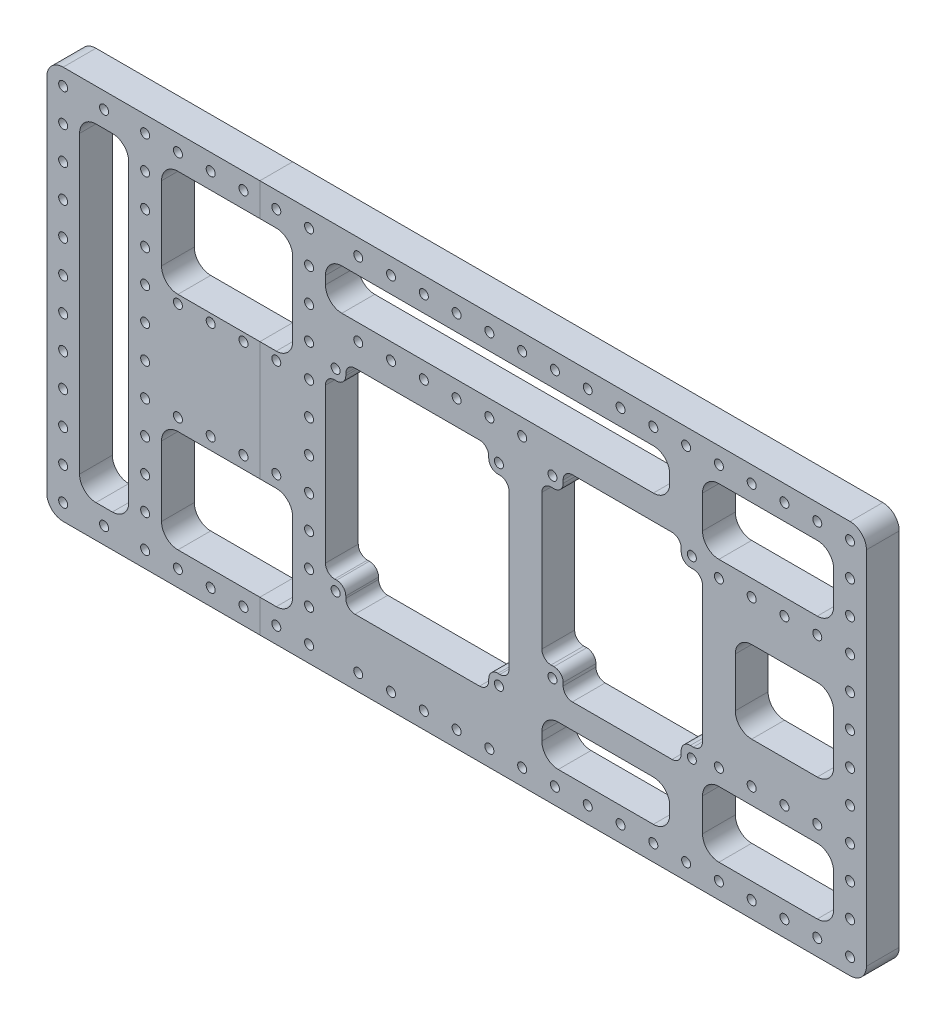
SolidWorks part; units mm, degrees
ref_plane "Alzado" through (0, 0, 0) normal (0, 0, 1) x (1, 0, 0)
ref_plane "Planta" through (0, 0, 0) normal (0, 1, 0) x (1, 0, 0)
ref_plane "Vista lateral" through (0, 0, 0) normal (1, 0, 0) x (0, 0, -1)
sketch "Croquis1" plane through (0, 0, 0) normal (0, 0, 1) x (1, 0, 0)
  line L1 (0, 0) -> (250, 0)
  line L2 (0, 0) -> (0, 120)
  line L3 (0, 120) -> (250, 120)
  line L4 (250, 0) -> (250, 120)
  dimension "D1" = 250
  dimension "D2" = 120
extrude "Saliente-Extruir1" add sketch "Croquis1" along normal blind 10
sketch "Croquis2" plane through (0, 0, 10) normal (0, 0, 1) x (1, 0, 0)
  line L0 (10, 110) -> (10, 10)
  line L1 (35, 110) -> (75, 110)
  line L2 (10, 10) -> (25, 10)
  line L3 (25, 110) -> (25, 10)
  line L5 (10, 110) -> (25, 110)
  line L6 (85, 110) -> (85, 97.5)
  line L7 (35, 10) -> (75, 10)
  line L8 (35, 10) -> (35, 110)
  line L9 (75, 110) -> (75, 10)
  line L10 (141, 20) -> (141, 85)
  line L11 (85, 110) -> (141, 110)
  line L12 (141, 20) -> (85, 20)
  line L13 (141, 85) -> (85, 85)
  line L14 (85, 85) -> (85, 20)
  line L15 (85, 97.5) -> (141, 97.5)
  line L16 (141, 97.5) -> (141, 110)
  line L18 (151, 25) -> (151, 95)
  line L23 (151, 95) -> (201, 95)
  line L24 (201, 95) -> (201, 25)
  line L25 (201, 25) -> (151, 25)
  dimension "D1" = 100
  dimension "D2" = 15
  dimension "D4" = 10
  dimension "D5" = 40
  dimension "D6" = 65
  dimension "D7" = 56
extrude "Cortar-Extruir1" cut sketch "Croquis2" against normal through all
sketch "Croquis6" plane through (0, 0, 10) normal (0, 0, 1) x (1, 0, 0)
  line L0 (75, 97.5) -> (35, 97.5)
  line L1 (75, 10) -> (75, 110) construction
  line L2 (35, 110) -> (35, 10) construction
  line L3 (35, 97.5) -> (35, 85)
  line L4 (35, 85) -> (75, 85)
  line L5 (75, 85) -> (75, 97.5)
extrude "Saliente-Extruir3" add sketch "Croquis6" against normal blind 10
sketch "Croquis7" plane through (0, 0, 10) normal (0, 0, 1) x (1, 0, 0)
  line L0 (151, 25) -> (151, 30)
  line L1 (151, 95) -> (151, 25) construction
  line L2 (151, 30) -> (201, 30)
  line L3 (201, 25) -> (201, 95) construction
  line L4 (201, 30) -> (201, 25)
  line L5 (201, 25) -> (151, 25)
  dimension "D1" = 5
extrude "Saliente-Extruir4" add sketch "Croquis7" against normal blind 10
sketch "Croquis8" plane through (0, 0, 10) normal (0, 0, 1) x (1, 0, 0)
  line L0 (151, 95) -> (151, 90)
  line L1 (151, 95) -> (151, 30) construction
  line L2 (151, 90) -> (201, 90)
  line L3 (201, 30) -> (201, 95) construction
  line L4 (201, 90) -> (201, 95)
  line L5 (201, 95) -> (151, 95)
  dimension "D1" = 5
extrude "Saliente-Extruir5" add sketch "Croquis8" against normal blind 10
sketch "Croquis10" plane through (0, 0, 10) normal (0, 0, 1) x (1, 0, 0)
  line L0 (200, 90) -> (200, 30)
  line L2 (240, 110) -> (200, 110)
  line L3 (201, 30) -> (151, 30) construction
  line L4 (200, 110) -> (200, 97.5)
  line L5 (200, 97.5) -> (240, 97.5)
  line L6 (240, 97.5) -> (240, 110)
  line L7 (200, 30) -> (201, 30)
  line L8 (151, 90) -> (201, 90) construction
  line L9 (200, 90) -> (201, 90)
  line L10 (201, 90) -> (201, 30)
  dimension "D1" = 1
  dimension "D2" = 40
extrude "Saliente-Extruir6" add sketch "Croquis10" against normal blind 10
sketch "Croquis11" plane through (0, 0, 10) normal (0, 0, 1) x (1, 0, 0)
  line L1 (200, 97.5) -> (200, 110)
  line L2 (200, 110) -> (240, 110)
  line L3 (240, 110) -> (240, 97.5)
  line L4 (240, 97.5) -> (200, 97.5)
  line L7 (240, 10) -> (240, 22.5)
  line L8 (240, 22.5) -> (200, 22.5)
  line L9 (200, 22.5) -> (200, 10)
  line L10 (200, 10) -> (240, 10)
  dimension "D1" = 40
extrude "Cortar-Extruir3" cut sketch "Croquis11" against normal through all
sketch "Croquis12" plane through (0, 0, 10) normal (0, 0, 1) x (1, 0, 0)
  line L1 (35, 85) -> (35, 10) construction
  line L2 (35, 72.5) -> (75, 72.5)
  line L3 (75, 10) -> (75, 85) construction
  line L4 (75, 72.5) -> (75, 85)
  line L5 (75, 85) -> (35, 85)
  line L6 (35, 85) -> (35, 72.5)
extrude "Saliente-Extruir7" add sketch "Croquis12" against normal blind 10
sketch "Croquis13" plane through (0, 0, 10) normal (0, 0, 1) x (1, 0, 0)
  line L1 (35, 72.5) -> (35, 10) construction
  line L2 (35, 47.5) -> (75, 47.5)
  line L3 (75, 10) -> (75, 72.5) construction
  line L4 (75, 47.5) -> (75, 22.5)
  line L5 (75, 22.5) -> (35, 22.5)
  line L6 (35, 22.5) -> (35, 47.5)
  dimension "D2" = 25
extrude "Saliente-Extruir9" add sketch "Croquis13" against normal blind 10
sketch "Croquis14" plane through (0, 0, 10) normal (0, 0, 1) x (1, 0, 0)
  line L0 (151, 110) -> (141, 110)
  line L1 (141, 110) -> (141, 97.5)
  line L2 (210, 30) -> (240, 30)
  line L3 (210, 30) -> (210, 90)
  line L4 (210, 90) -> (240, 90)
  line L5 (240, 30) -> (240, 90)
  line L6 (141, 97.5) -> (141, 110) construction
  line L7 (151, 110) -> (190, 110)
  line L8 (141, 97.5) -> (151, 97.5)
  line L9 (151, 97.5) -> (190, 97.5)
  line L10 (190, 110) -> (190, 97.5)
  line L11 (190, 22.5) -> (151, 22.5)
  line L12 (151, 22.5) -> (151, 10)
  line L13 (151, 10) -> (190, 10)
  line L14 (190, 10) -> (190, 22.5)
  dimension "D1" = 60
extrude "Cortar-Extruir4" cut sketch "Croquis14" against normal through all
fillet "Redondeo4" radius 5 38 edges at (10, 110, 5) (35, 72.5, 5) (85, 97.5, 5) (35, 110, 5) (85, 110, 5) (200, 22.5, 5) (210, 90, 5) (200, 110, 5) (210, 30, 5) (240, 30, 5) (240, 10, 5) (240, 97.5, 5) (190, 10, 5) (190, 97.5, 5) (25, 10, 5) (75, 97.5, 5) (75, 47.5, 5) (75, 10, 5) (10, 10, 5) (35, 97.5, 5) (35, 47.5, 5) (35, 10, 5) (151, 10, 5) (200, 10, 5) (200, 97.5, 5) (190, 22.5, 5) (240, 22.5, 5) (240, 90, 5) (240, 110, 5) (190, 110, 5) (75, 22.5, 5) (75, 72.5, 5) (75, 110, 5) (25, 110, 5) (0, 120, 5) (0, 0, 5) (250, 0, 5) (250, 120, 5)
fillet "Redondeo5" radius 5 2 edges at (35, 22.5, 5) (151, 22.5, 5)
sketch "Croquis16" plane through (0, 0, 10) normal (0, 0, 1) x (1, 0, 0)
  line L0 (85, 20) -> (91.2, 20)
  line L1 (85, 20) -> (141, 20) construction
  line L2 (91.2, 20) -> (91.2, 26.2)
  line L3 (91.2, 26.2) -> (85, 26.2)
  line L4 (85, 85) -> (85, 20) construction
  line L5 (85, 26.2) -> (85, 20)
  line L9 (134.8, 26.2) -> (141, 26.2)
  line L10 (141, 20) -> (134.8, 20)
  line L11 (141, 26.2) -> (141, 20)
  line L12 (134.8, 20) -> (134.8, 26.2)
  line L13 (141, 78.8) -> (141, 85)
  line L14 (134.8, 78.8) -> (141, 78.8)
  line L15 (134.8, 85) -> (134.8, 78.8)
  line L16 (141, 85) -> (134.8, 85)
  line L17 (85, 85) -> (91.2, 85)
  line L18 (85, 78.8) -> (85, 85)
  line L19 (91.2, 78.8) -> (85, 78.8)
  line L20 (91.2, 85) -> (91.2, 78.8)
  dimension "D1" = 6.2
  dimension "D2" = 6.2
extrude "Saliente-Extruir10" add sketch "Croquis16" against normal blind 10
sketch "Croquis17" plane through (0, 0, 10) normal (0, 0, 1) x (1, 0, 0)
  line L1 (151, 90) -> (157.5, 90)
  line L2 (151, 90) -> (151, 83.5)
  line L3 (151, 83.5) -> (157.5, 83.5)
  line L4 (157.5, 90) -> (157.5, 83.5)
  line L10 (151, 30) -> (151, 36.5)
  line L11 (151, 30) -> (157.5, 30)
  line L12 (157.5, 30) -> (157.5, 36.5)
  line L13 (151, 36.5) -> (157.5, 36.5)
  line L14 (193.5, 90) -> (193.5, 83.5)
  line L15 (200, 83.5) -> (193.5, 83.5)
  line L16 (200, 90) -> (200, 83.5)
  line L17 (200, 90) -> (193.5, 90)
  line L18 (200, 36.5) -> (193.5, 36.5)
  line L19 (193.5, 30) -> (193.5, 36.5)
  line L20 (200, 30) -> (193.5, 30)
  line L21 (200, 30) -> (200, 36.5)
  dimension "D1" = 6.5
  dimension "D2" = 6.5
extrude "Saliente-Extruir12" add sketch "Croquis17" against normal blind 10
fillet "Redondeo6" radius 2.8 8 edges at (157.5, 83.5, 5) (157.5, 36.5, 5) (193.5, 36.5, 5) (193.5, 83.5, 5) (134.8, 26.2, 5) (134.8, 78.8, 5) (91.2, 26.2, 5) (91.2, 78.8, 5)
fillet "Redondeo7" radius 2.8 14 edges at (193.5, 30, 5) (200, 36.5, 5) (200, 83.5, 5) (193.5, 90, 5) (134.8, 85, 5) (141, 78.8, 5) (141, 26.2, 5) (134.8, 20, 5) (157.5, 30, 5) (151, 36.5, 5) (91.2, 20, 5) (85, 26.2, 5) (85, 78.8, 5) (91.2, 85, 5)
fillet "Redondeo8" radius 2.8 2 edges at (151, 83.5, 5) (157.5, 90, 5)
sketch "Croquis18" plane through (0, 0, 10) normal (0, 0, 1) x (1, 0, 0)
  circle A0 centre (137.9, 23.1) radius 1.375
  circle A1 centre (88.1, 23.1) radius 1.375
  circle A2 centre (88.1, 81.9) radius 1.375
  circle A3 centre (137.9, 81.9) radius 1.375
  circle A4 centre (154.25, 33.25) radius 1.375
  circle A5 centre (196.75, 33.25) radius 1.375
  circle A6 centre (196.75, 86.75) radius 1.375
  circle A7 centre (154.25, 86.75) radius 1.375
  dimension "D1" = 2.75
extrude "Cortar-Extruir5" cut sketch "Croquis18" against normal through all
sketch "Croquis19" plane through (0, 0, 10) normal (0, 0, 1) x (1, 0, 0)
  line L0 (240, 72.5) -> (210, 72.5)
  line L1 (240, 35) -> (240, 85) construction
  line L3 (240, 47.5) -> (210, 47.5)
  line L4 (210, 30) -> (240, 30)
  line L5 (240, 90) -> (240, 72.5)
  line L6 (240, 30) -> (240, 47.5)
  line L7 (210, 85) -> (210, 35) construction
  line L8 (210, 72.5) -> (210, 90)
  line L9 (210, 90) -> (240, 90)
  line L10 (210, 47.5) -> (210, 30)
extrude "Saliente-Extruir13" add sketch "Croquis19" against normal blind 10
sketch "Croquis20" plane through (0, 0, 10) normal (0, 0, 1) x (1, 0, 0)
  line L0 (200, 10) -> (240, 10)
  line L2 (200, 10) -> (200, 30)
  line L3 (200, 30) -> (240, 30)
  line L4 (240, 10) -> (240, 30)
  line L7 (240, 110) -> (240, 90)
  line L8 (200, 90) -> (240, 90)
  line L9 (200, 110) -> (200, 90)
  line L10 (200, 110) -> (240, 110)
extrude "Cortar-Extruir7" cut sketch "Croquis20" against normal through all
fillet "Redondeo9" radius 5 12 edges at (200, 10, 5) (210, 47.5, 5) (200, 90, 5) (240, 10, 5) (240, 47.5, 5) (240, 90, 5) (240, 30, 5) (240, 72.5, 5) (240, 110, 5) (200, 30, 5) (200, 110, 5) (210, 72.5, 5)
sketch "Croquis21" plane through (0, 0, 10) normal (0, 0, 1) x (1, 0, 0)
  circle A2 centre (5, 115) radius 1.375
  circle A3 centre (5, 105) radius 1.375
  circle A4 centre (5, 95) radius 1.375
  circle A5 centre (5, 85) radius 1.375
  circle A6 centre (5, 75) radius 1.375
  circle A7 centre (5, 65) radius 1.375
  circle A8 centre (5, 55) radius 1.375
  circle A9 centre (5, 45) radius 1.375
  circle A10 centre (5, 35) radius 1.375
  circle A11 centre (5, 25) radius 1.375
  circle A12 centre (5, 15) radius 1.375
  circle A13 centre (5, 5) radius 1.375
  circle A14 centre (245, 5) radius 1.375
  circle A15 centre (245, 15) radius 1.375
  circle A16 centre (245, 25) radius 1.375
  circle A17 centre (245, 35) radius 1.375
  circle A18 centre (245, 45) radius 1.375
  circle A19 centre (245, 55) radius 1.375
  circle A20 centre (245, 65) radius 1.375
  circle A21 centre (245, 75) radius 1.375
  circle A22 centre (245, 85) radius 1.375
  circle A23 centre (245, 95) radius 1.375
  circle A24 centre (245, 105) radius 1.375
  circle A25 centre (245, 115) radius 1.375
  circle A26 centre (15, 115) radius 1.375
  circle A27 centre (25, 115) radius 1.375
  circle A28 centre (35, 115) radius 1.375
  circle A29 centre (45, 115) radius 1.375
  circle A30 centre (55, 115) radius 1.375
  circle A31 centre (65, 115) radius 1.375
  circle A32 centre (75, 115) radius 1.375
  circle A33 centre (85, 115) radius 1.375
  circle A34 centre (95, 115) radius 1.375
  circle A35 centre (105, 115) radius 1.375
  circle A36 centre (115, 115) radius 1.375
  circle A37 centre (125, 115) radius 1.375
  circle A38 centre (135, 115) radius 1.375
  circle A39 centre (145, 115) radius 1.375
  circle A40 centre (155, 115) radius 1.375
  circle A41 centre (165, 115) radius 1.375
  circle A42 centre (175, 115) radius 1.375
  circle A43 centre (185, 115) radius 1.375
  circle A44 centre (195, 115) radius 1.375
  circle A45 centre (205, 115) radius 1.375
  circle A46 centre (215, 115) radius 1.375
  circle A47 centre (225, 115) radius 1.375
  circle A48 centre (235, 115) radius 1.375
  circle A49 centre (235, 5) radius 1.375
  circle A50 centre (225, 5) radius 1.375
  circle A51 centre (215, 5) radius 1.375
  circle A52 centre (205, 5) radius 1.375
  circle A53 centre (195, 5) radius 1.375
  circle A54 centre (185, 5) radius 1.375
  circle A55 centre (175, 5) radius 1.375
  circle A56 centre (165, 5) radius 1.375
  circle A57 centre (155, 5) radius 1.375
  circle A58 centre (145, 5) radius 1.375
  circle A59 centre (135, 5) radius 1.375
  circle A60 centre (125, 5) radius 1.375
  circle A61 centre (115, 5) radius 1.375
  circle A62 centre (105, 5) radius 1.375
  circle A63 centre (95, 5) radius 1.375
  circle A64 centre (85, 5) radius 1.375
  circle A65 centre (75, 5) radius 1.375
  circle A66 centre (65, 5) radius 1.375
  circle A67 centre (55, 5) radius 1.375
  circle A68 centre (45, 5) radius 1.375
  circle A69 centre (35, 5) radius 1.375
  circle A70 centre (25, 5) radius 1.375
  circle A71 centre (15, 5) radius 1.375
  dimension "D1" = 24
  dimension "D2" = 12
extrude "Cortar-Extruir8" cut sketch "Croquis21" against normal through all
sketch "Croquis22" plane through (0, 0, 10) normal (0, 0, 1) x (1, 0, 0)
  line L0 (35, 16.25) -> (75, 16.25)
  line L1 (35, 17.5) -> (35, 15) construction
  line L2 (75, 15) -> (75, 17.5) construction
  line L3 (75, 16.25) -> (75, 38.2484)
  line L4 (35, 102.5) -> (35, 16.25)
  line L5 (35, 102.5) -> (75, 102.5)
  line L6 (75, 102.5) -> (75, 38.2484)
extrude "Saliente-Extruir14" add sketch "Croquis22" against normal blind 10
sketch "Croquis23" plane through (0, 0, 10) normal (0, 0, 1) x (1, 0, 0)
  line L1 (35, 16.25) -> (75, 16.25)
  line L2 (35, 16.25) -> (35, 41.25)
  line L3 (35, 41.25) -> (75, 41.25)
  line L4 (75, 16.25) -> (75, 41.25)
  line L5 (35, 102.5) -> (75, 102.5)
  line L6 (35, 102.5) -> (35, 77.5)
  line L7 (35, 77.5) -> (75, 77.5)
  line L8 (75, 102.5) -> (75, 77.5)
  dimension "D1" = 25
  dimension "D2" = 25
extrude "Cortar-Extruir9" cut sketch "Croquis23" against normal through all
fillet "Redondeo10" radius 5 4 edges at (35, 77.5, 5) (75, 77.5, 5) (75, 41.25, 5) (35, 41.25, 5)
sketch "Croquis24" plane through (0, 0, 10) normal (0, 0, 1) x (1, 0, 0)
  circle A0 centre (30, 105) radius 1.375
  circle A1 centre (30, 95) radius 1.375
  circle A2 centre (30, 85) radius 1.375
  circle A3 centre (30, 75) radius 1.375
  circle A4 centre (30, 65) radius 1.375
  circle A5 centre (30, 55) radius 1.375
  circle A6 centre (30, 45) radius 1.375
  circle A7 centre (30, 35) radius 1.375
  circle A8 centre (30, 25) radius 1.375
  circle A9 centre (30, 15) radius 1.375
  dimension "D1" = 2.75
  dimension "D2" = 10
extrude "Cortar-Extruir10" cut sketch "Croquis24" against normal through all
sketch "Croquis25" plane through (0, 0, 10) normal (0, 0, 1) x (1, 0, 0)
  circle A0 centre (80, 75) radius 1.375
  circle A1 centre (80, 65) radius 1.375
  circle A2 centre (80, 55) radius 1.375
  circle A3 centre (80, 45) radius 1.375
  circle A4 centre (80, 85) radius 1.375
  circle A5 centre (80, 95) radius 1.375
  circle A6 centre (80, 105) radius 1.375
  circle A7 centre (80, 35) radius 1.375
  circle A8 centre (80, 25) radius 1.375
  circle A9 centre (80, 15) radius 1.375
  dimension "D1" = 2.75
  dimension "D2" = 4
  dimension "D3" = 3
  dimension "D4" = 2
  dimension "D5" = 4
extrude "Cortar-Extruir12" cut sketch "Croquis25" against normal through all
sketch "Croquis26" plane through (0, 0, 10) normal (0, 0, 1) x (1, 0, 0)
  circle A1 centre (183.625, 93.6429) radius 1.375
  circle A2 centre (173.625, 93.6429) radius 1.375
  circle A3 centre (163.625, 93.6429) radius 1.375
  circle A4 centre (153.625, 93.6429) radius 1.375
  circle A5 centre (143.625, 93.6429) radius 1.375
  circle A6 centre (133.625, 93.6429) radius 1.375
  circle A7 centre (123.625, 93.6429) radius 1.375
  circle A8 centre (113.625, 93.6429) radius 1.375
  circle A9 centre (103.625, 93.6429) radius 1.375
  circle A10 centre (93.625, 93.6429) radius 1.375
  dimension "D1" = 2.75
  dimension "D2" = 10
extrude "Cortar-Extruir13" cut sketch "Croquis26" against normal through all
sketch "Croquis29" plane through (0, 0, 10) normal (0, 0, 1) x (1, 0, 0)
  circle A0 centre (70, 75) radius 1.375
  circle A1 centre (40, 45) radius 1.375
  circle A2 centre (50, 45) radius 1.375
  circle A3 centre (60, 45) radius 1.375
  circle A4 centre (70, 45) radius 1.375
  circle A5 centre (60, 75) radius 1.375
  circle A6 centre (50, 75) radius 1.375
  circle A7 centre (40, 75) radius 1.375
extrude "Cortar-Extruir14" cut sketch "Croquis29" against normal blind 10
sketch "Croquis30" plane through (0, 0, 10) normal (0, 0, 1) x (1, 0, 0)
  circle A0 centre (205, 35) radius 1.375
  circle A1 centre (235, 85) radius 1.375
  circle A2 centre (225, 85) radius 1.375
  circle A3 centre (215, 85) radius 1.375
  circle A4 centre (205, 85) radius 1.375
  circle A5 centre (215, 35) radius 1.375
  circle A6 centre (225, 35) radius 1.375
  circle A7 centre (235, 35) radius 1.375
extrude "Cortar-Extruir15" cut sketch "Croquis30" against normal through all
sketch "Croquis35" plane through (0, 0, 10) normal (0, 0, 1) x (1, 0, 0)
  line L1 (11.3529, 7.7785) -> (198.8215, 7.7785)
  line L2 (11.3529, 7.7785) -> (11.3529, 2.2832)
  line L3 (11.3529, 2.2832) -> (198.8215, 2.2832)
  line L4 (198.8215, 7.7785) -> (198.8215, 2.2832)
  line L5 (11.3529, 118.1029) -> (87.653, 118.1029)
  line L6 (11.3529, 118.1029) -> (11.3529, 112.0945)
  line L7 (11.3529, 112.0945) -> (87.653, 112.0945)
  line L8 (87.653, 118.1029) -> (87.653, 112.0945)
extrude "Saliente-Extruir18" add sketch "Croquis35" against normal blind 10
sketch "Croquis36" plane through (0, 0, 10) normal (0, 0, 1) x (1, 0, 0)
  circle A0 centre (70, 115) radius 1.375
  circle A1 centre (60, 115) radius 1.375
  circle A2 centre (50, 115) radius 1.375
  circle A3 centre (40, 115) radius 1.375
  circle A4 centre (30, 115) radius 1.375
  circle A5 centre (80, 115) radius 1.375
  circle A6 centre (80, 5) radius 1.375
  circle A7 centre (30, 5) radius 1.375
  circle A8 centre (40, 5) radius 1.375
  circle A9 centre (50, 5) radius 1.375
  circle A10 centre (60, 5) radius 1.375
  circle A11 centre (70, 5) radius 1.375
  circle A12 centre (17.484, 5.0668) radius 1.375
  circle A13 centre (17.4813, 115.0286) radius 1.375
  dimension "D1" = 2.75
  dimension "D2" = 5
  dimension "D3" = 2
extrude "Cortar-Extruir16" cut sketch "Croquis36" against normal through all
sketch "Croquis37" plane through (0, 0, 10) normal (0, 0, 1) x (1, 0, 0)
  line L1 (87.3781, 96.1662) -> (187.5191, 96.1662)
  line L2 (87.3781, 96.1662) -> (87.3781, 91.7523)
  line L3 (87.3781, 91.7523) -> (187.5191, 91.7523)
  line L4 (187.5191, 96.1662) -> (187.5191, 91.7523)
extrude "Saliente-Extruir19" add sketch "Croquis37" against normal blind 10
sketch "Croquis39" plane through (0, 0, 10) normal (0, 0, 1) x (1, 0, 0)
  circle A0 centre (105, 92.5) radius 1.375
  circle A1 centre (95, 92.5) radius 1.375
  circle A2 centre (115, 92.5) radius 1.375
  circle A3 centre (125, 92.5) radius 1.375
  circle A4 centre (135, 92.5) radius 1.375
  circle A5 centre (145, 92.5) radius 1.375
  dimension "D1" = 6
extrude "Cortar-Extruir17" cut sketch "Croquis39" against normal blind 10
sketch "Croquis40" plane through (0, 0, 10) normal (0, 0, 1) x (1, 0, 0)
  circle A1 centre (95, 5) radius 1.375
  circle A2 centre (105, 5) radius 1.375
  circle A3 centre (115, 5) radius 1.375
  circle A4 centre (125, 5) radius 1.375
  circle A5 centre (135, 5) radius 1.375
  circle A6 centre (145, 5) radius 1.375
  circle A7 centre (155, 5) radius 1.375
  circle A8 centre (165, 5) radius 1.375
  circle A9 centre (175, 5) radius 1.375
  circle A10 centre (185, 5) radius 1.375
  circle A11 centre (195, 5) radius 1.375
  dimension "D1" = 11
extrude "Cortar-Extruir18" cut sketch "Croquis40" against normal through all
sketch "Croquis41" plane through (0, 0, 10) normal (0, 0, 1) x (1, 0, 0)
  line L3 (5, 0) -> (245, 0) construction
  line L5 (245, 120) -> (5, 120) construction
  line L6 (65, 0) -> (65, 120)
split "Partir1" trim tools "Croquis41" bodies to split 138 resulting bodies 139 140
